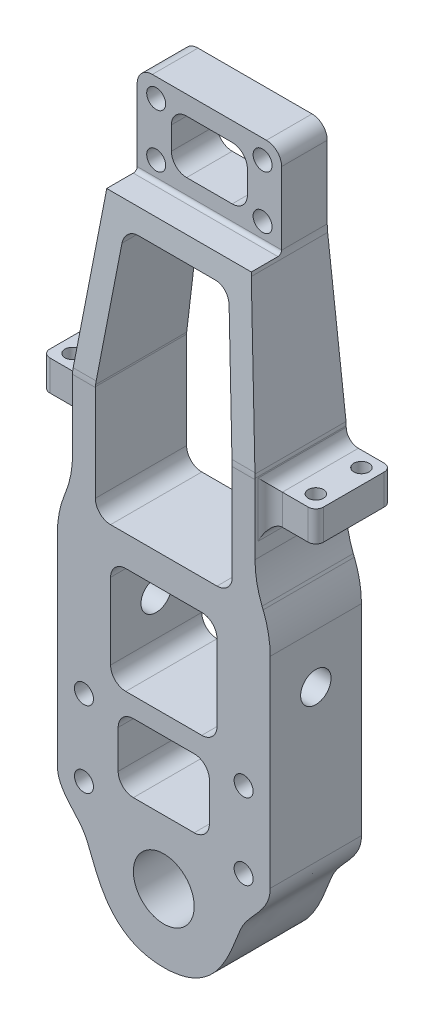
SolidWorks part; units mm, degrees
material "6061-T6 (SS)"
ref_plane "Front Plane" through (0, 0, 0) normal (0, 0, 1) x (1, 0, 0)
ref_plane "Top Plane" through (0, 0, 0) normal (0, 1, 0) x (1, 0, 0)
ref_plane "Right Plane" through (0, 0, 0) normal (1, 0, 0) x (0, 0, -1)
sketch "Sketch1" plane through (0, 0, 0) normal (0, 0, 1) x (1, 0, 0)
  line L0 (0, 0) -> (0, 168.402) construction
  line L1 (0, 0) -> (0, -85.725) construction
  line L2 (-22.225, 22.225) -> (22.225, 22.225)
  line L3 (-22.225, 22.225) -> (-22.225, -22.225)
  line L4 (-22.225, -22.225) -> (22.225, -22.225)
  line L5 (22.225, 22.225) -> (22.225, -22.225)
  line L6 (-38.1, 187.452) -> (38.1, 187.452) construction
  line L7 (-38.1, 187.452) -> (-38.1, -114.173) construction
  line L8 (-38.1, -114.173) -> (38.1, -114.173)
  line L9 (38.1, 187.452) -> (38.1, -114.173) construction
  line L10 (0, 0) -> (64.3201, 0) construction
  line L11 (-30.1625, 187.452) -> (-30.1625, 149.352)
  line L12 (-30.1625, 149.352) -> (-38.1, 82.55)
  line L13 (-38.1, 82.55) -> (-38.1, -114.173)
  line L15 (38.1, 82.55) -> (38.1, -114.173)
  line L16 (30.1625, 149.352) -> (38.1, 82.55)
  line L17 (30.1625, 187.452) -> (30.1625, 149.352)
  line L18 (-30.1625, 187.452) -> (30.1625, 187.452)
  circle A0 centre (0, -85.725) radius 12.7
  dimension "D10" = 25.4
  dimension "D1" = 168.402
  dimension "D2" = 28.448
  dimension "D3" = 44.45
  dimension "D4" = 44.45
  dimension "D5" = 301.625
  dimension "D6" = 76.2
  dimension "D7" = 38.1
  dimension "D8" = 19.05
  dimension "D9" = 85.725
  dimension "D11" = 60.325
  dimension "D12" = 82.55
  dimension "D13" = 66.802
extrude "Boss-Extrude1" add sketch "Sketch1" along normal blind 38.1
fillet "Fillet13" radius 25.4 2 edges at (30.1625, 149.352, 19.05) (-30.1625, 149.352, 19.05)
sketch "Sketch2" plane through (0, 0, 0) normal (1, 0, 0) x (0, 0, -1)
  line L0 (-19.05, 187.452) -> (-19.05, 149.352)
  line L2 (-19.05, 149.352) -> (-38.1, 149.352)
  line L4 (-38.1, 149.352) -> (-38.1, 187.452)
  line L5 (-38.1, 187.452) -> (-19.05, 187.452)
  line L6 (-38.1, 150.8557) -> (-38.1, 187.452) construction
  line L7 (-38.1, 187.452) -> (0, 187.452) construction
  dimension "D1" = 38.1
  dimension "D2" = 19.05
extrude "Cut-Extrude1" cut sketch "Sketch2" against normal through all and the other way through all
sketch "Sketch3" plane through (0, 0, 19.05) normal (0, 0, 1) x (1, 0, 0)
  line L1 (-30.1625, 168.402) -> (30.1625, 168.402) construction
  line L5 (0, 168.402) -> (0, 187.452) construction
  line L6 (-30.1625, 187.452) -> (30.1625, 187.452) construction
  line L7 (-30.1625, 150.8557) -> (-30.1625, 187.452) construction
  circle A0 centre (-22.225, 179.5145) radius 3.9688
  circle A1 centre (22.225, 179.5145) radius 3.9687
  circle A2 centre (-22.225, 157.2895) radius 3.9688
  circle A3 centre (22.225, 157.2895) radius 3.9687
  dimension "D9" = 7.9375
  dimension "D1" = 22.225
  dimension "D2" = 11.1125
extrude "Cut-Extrude2" cut sketch "Sketch3" against normal through all
sketch "Sketch4" plane through (-22.225, 0, 0) normal (1, 0, 0) x (0, 0, -1)
  line L1 (-38.1, 22.225) -> (-38.1, -22.225) construction
  circle A0 centre (-19.05, 0) radius 6.35
  dimension "D3" = 12.7
  dimension "D2" = 19.05
extrude "Cut-Extrude3" cut sketch "Sketch4" against normal through all and the other way through all
sketch "Sketch5" plane through (0, 0, 38.1) normal (0, 0, 1) x (1, 0, 0)
  line L0 (-38.1, -114.173) -> (-44.45, -114.173)
  line L1 (-44.45, -114.173) -> (-44.45, 28.575)
  line L2 (38.1, -114.173) -> (44.45, -114.173)
  line L3 (44.45, -114.173) -> (44.45, 28.575)
  line L4 (-44.45, 28.575) -> (-38.1, 44.45)
  line L5 (44.45, 28.575) -> (38.1, 44.45)
  line L6 (-38.1, 44.45) -> (-38.1, -114.173)
  line L7 (38.1, 44.45) -> (38.1, -114.173)
  line L8 (22.225, 22.225) -> (-22.225, 22.225) construction
  dimension "D1" = 6.35
  dimension "D3" = 22.225
  dimension "D4" = 15.875
extrude "Boss-Extrude2" add sketch "Sketch5" against normal up to surface (38.1 mm away) contours L1 L0 | L3 L2 region at (-41.2193, -38.7606, 38.1) region at (41.2193, -38.7606, 38.1) up to face at (26.1937, 157.2895, 0)
sketch "Sketch6" plane through (-22.225, 0, 0) normal (1, 0, 0) x (0, 0, -1)
  circle A0 centre (-19.05, 0) radius 6.35
  circle A1 centre (-19.05, 0) radius 6.35 construction
extrude "Cut-Extrude4" cut sketch "Sketch6" against normal through all and the other way through all
sketch "Sketch7" plane through (0, 0, 38.1) normal (0, 0, 1) x (1, 0, 0)
  line L0 (-28.575, 34.925) -> (-28.575, 81.9861) construction
  line L1 (-21.7023, 139.827) -> (21.7023, 139.827) construction
  line L2 (-28.575, 81.9861) -> (-21.7023, 139.827) construction
  line L3 (-28.575, 34.925) -> (28.575, 34.925) construction
  line L4 (28.575, 81.9861) -> (21.7023, 139.827) construction
  line L5 (28.575, 34.925) -> (28.575, 81.9861) construction
  line L6 (-30.2071, 149.352) -> (30.2071, 149.352) construction
  line L7 (22.225, 22.225) -> (-22.225, 22.225) construction
  line L8 (0, 0) -> (0, 134.3942) construction
  line L9 (-26.0738, 103.0362) -> (-35.5323, 104.1601) construction
  line L10 (-19.05, -30.48) -> (19.05, -30.48)
  line L11 (-19.05, -30.48) -> (-19.05, -59.055)
  line L12 (-19.05, -59.055) -> (19.05, -59.055)
  line L13 (19.05, -30.48) -> (19.05, -59.055)
  line L14 (-30.3399, 147.8588) -> (-38.1, 82.55) construction
  line L15 (-28.575, 61.5413) -> (-38.1, 61.5413) construction
  line L16 (-38.1, 82.55) -> (-38.1, 44.45) construction
  point P15 (0, 139.827)
  point P19 (0, 34.925)
  dimension "D1" = 9.525
  dimension "D2" = 38.1
  dimension "D3" = 9.525
  dimension "D4" = 12.7
  dimension "D5" = 30.48
  dimension "D6" = 28.575
  dimension "D7" = 57.15
extrude "Cut-Extrude5" cut sketch "Sketch7" against normal offset from surface (33.3375 mm away) 4.7625 up to face at (26.1937, 157.2895, 0)
sketch "Sketch20" plane through (0, 0, 38.1) normal (0, 0, 1) x (1, 0, 0)
  line L0 (-28.575, 81.9861) -> (-21.7023, 139.827) construction
  line L1 (-21.7023, 139.827) -> (21.7023, 139.827) construction
  line L2 (28.575, 81.9861) -> (21.7023, 139.827) construction
  line L3 (28.575, 34.925) -> (28.575, 81.9861) construction
  line L4 (-28.575, 34.925) -> (28.575, 34.925) construction
  line L5 (-28.575, 34.925) -> (-28.575, 81.9861) construction
  line L6 (-28.575, 81.9861) -> (-21.7023, 139.827)
  line L7 (-21.7023, 139.827) -> (21.7023, 139.827)
  line L8 (28.575, 81.9861) -> (21.7023, 139.827)
  line L9 (28.575, 34.925) -> (28.575, 81.9861)
  line L10 (-28.575, 34.925) -> (28.575, 34.925)
  line L11 (-28.575, 34.925) -> (-28.575, 81.9861)
extrude "Cut-Extrude13" cut sketch "Sketch20" against normal through all
fillet "Fillet1" radius 6.35 10 edges at (19.05, -59.055, 21.4313) (19.05, -30.48, 21.4313) (-19.05, -30.48, 21.4313) (-19.05, -59.055, 21.4313) (-28.575, 34.925, 19.05) (28.575, 34.925, 19.05) (21.7023, 139.827, 19.05) (-21.7023, 139.827, 19.05)
fillet "Fillet5" radius 41.275 4 edges at (44.45, 28.575, 19.05) (-44.45, 28.575, 19.05)
sketch "Sketch13" plane through (0, 0, 0) normal (1, 0, 0) x (0, 0, -1)
  circle A0 centre (-19.05, 0) radius 6.35 construction
  circle A1 centre (-19.05, 0) radius 6.35
sketch "Sketch14" plane through (0, 0, 38.1) normal (0, 0, 1) x (1, 0, 0)
  line L0 (0, 0) -> (0, -85.725) construction
  line L1 (56.1407, -47.625) -> (0, -47.625) construction
  line L2 (0, 0) -> (0, -85.725) construction
  circle A0 centre (33.3375, -31.75) radius 3.9687
  circle A1 centre (33.3375, -63.5) radius 3.9687
  circle A2 centre (-33.3375, -63.5) radius 3.9688
  circle A3 centre (-33.3375, -31.75) radius 3.9688
  dimension "D4" = 7.9375
  dimension "D1" = 47.625
  dimension "D2" = 31.75
  dimension "D3" = 66.675
extrude "Cut-Extrude9" cut sketch "Sketch14" against normal blind 19.05
fillet "Fillet4" radius 6.35 4 edges at (-22.225, -22.225, 19.05) (22.225, -22.225, 19.05) (22.225, 22.225, 19.05) (-22.225, 22.225, 19.05)
sketch "Sketch15" plane through (38.1, 0, 0) normal (1, 0, 0) x (0, 0, -1)
  line L1 (0, 52.3988) -> (0, 82.55) construction
  line L2 (0, 76.2) -> (-31.75, 76.2)
  line L3 (-31.75, 76.2) -> (-31.75, 63.5)
  line L4 (-31.75, 63.5) -> (0, 63.5)
  line L5 (-31.75, 69.85) -> (0, 69.85) construction
  line L6 (-15.875, 69.85) -> (-15.875, 6.3089) construction
  line L7 (0, 63.5) -> (0, 76.2)
  dimension "D1" = 12.7
  dimension "D2" = 31.75
  dimension "D3" = 69.85
extrude "Boss-Extrude3" add sketch "Sketch15" along normal blind 19.05
sketch "Sketch16" plane through (0, 76.2, 0) normal (0, 1, 0) x (1, 0, 0)
  line L0 (57.15, -15.875) -> (38.8119, -15.875) construction
  line L1 (57.15, 0) -> (57.15, -31.75) construction
  line L2 (50.8, -6.35) -> (50.8, -25.4) construction
  line L4 (45.2437, -9.5579) -> (50.8, -12.7658) construction
  line L5 (50.8, -12.7658) -> (56.3562, -9.5579) construction
  line L6 (56.3562, -9.5579) -> (56.3562, -3.1421) construction
  line L7 (56.3562, -3.1421) -> (50.8, 0.0658) construction
  line L8 (50.8, 0.0658) -> (45.2437, -3.1421) construction
  line L9 (45.2437, -3.1421) -> (45.2437, -9.5579) construction
  circle A0 centre (50.8, -6.35) radius 3.175
  circle A1 centre (50.8, -25.4) radius 3.175
  circle A2 centre (50.8, -6.35) radius 6.4158 construction
  point P8 (50.8, -15.875)
  dimension "D1" = 6.35
  dimension "D2" = 19.05
  dimension "D3" = 11.1125
  dimension "D4" = 6.35
extrude "Cut-Extrude10" cut sketch "Sketch16" against normal up to next
mirror "Mirror4" about plane through (0, 0, 0) normal (1, 0, 0) of "Cut-Extrude10", "Boss-Extrude3"
fillet "Fillet11" radius 12.7 2 edges at (-38.1, 82.55, 19.05) (38.1, 82.55, 19.05)
fillet "Fillet6" radius 5.08 4 edges at (-38.1, 76.2, 15.875) (-38.1, 63.5, 15.875) (38.1, 63.5, 15.875) (38.1, 76.2, 15.875)
fillet "Fillet7" radius 5.08 2 edges at (-38.1, 69.85, 31.75) (38.1, 69.85, 31.75)
fillet "Fillet8" radius 3.175 4 edges at (57.15, 69.85, 31.75) (-57.15, 69.85, 31.75) (57.15, 69.85, 0) (-57.15, 69.85, 0)
ref_point "Point1"
sketch "Sketch17" plane through (0, 0, 0) normal (0, 0, 1) x (1, 0, 0)
  line L0 (0, -85.725) -> (9.726, 37.8549)
  line L1 (0, -85.725) -> (0, 0) construction
  dimension "D1" = 4.5
chamfer "Chamfer1" distance 66.802 distance2 6.35 1 edges at (0, 149.352, 38.1) first distance on face at (-37.3062, -31.75, 38.1)
fillet "Fillet9" radius 25.4 2 edges at (-33.2929, 82.55, 38.1) (33.2929, 82.55, 38.1)
fillet "Fillet10" radius 1.5875 8 edges at (-17.1901, -32.3399, 4.7625) (-19.05, -44.7675, 4.7625) (-17.1901, -57.1951, 4.7625) (0, -59.055, 4.7625) (17.1901, -57.1951, 4.7625) (19.05, -44.7675, 4.7625) (17.1901, -32.3399, 4.7625) (0, -30.48, 4.7625)
sketch "Sketch18" plane through (0, 0, 38.1) normal (0, 0, 1) x (1, 0, 0)
  line L0 (-44.45, -114.173) -> (44.45, -114.173) construction
  line L1 (-44.45, -114.173) -> (-44.45, 20.6262) construction
  line L2 (44.45, -114.173) -> (44.45, 20.6262) construction
  line L3 (-44.45, -114.173) -> (44.45, -114.173)
  line L4 (-44.45, -114.173) -> (-44.45, -63.2897)
  line L5 (44.45, -114.173) -> (44.45, -63.2897)
  line L6 (0, -85.725) -> (0, 0) construction
  line L7 (-6.757, -114.173) -> (6.787, -114.173) construction
  line L8 (44.45, -70.2557) -> (44.45, -44.5652) construction
  line L9 (0, -114.173) -> (0, 0) construction
  circle A0 centre (0, -69.723) radius 44.45 construction
  circle A1 centre (0, -85.725) radius 25.4 construction
  spline S0 degree 3 poles (44.45, -63.2897) (44.45, -70.6109) (36.9805, -76.2293) (28.9235, -88.5672) (23.7898, -114.173) (0, -114.173) knots 0 0 0 0 0.400028 0.500028 1 1 1 1
  spline S1 degree 3 poles (-44.45, -63.2897) (-44.45, -70.6109) (-36.9805, -76.2293) (-28.9235, -88.5672) (-23.7898, -114.173) (0, -114.173) knots 0 0 0 0 0.400028 0.500028 1 1 1 1
  line M27 (-44.45, 20.6262) -> (-44.45, -114.173)
  line M28 (-44.45, -114.173) -> (44.45, -114.173)
  line M29 (44.45, -114.173) -> (44.45, 20.6262)
  dimension "D1" = 50.8
extrude "Cut-Extrude11" cut sketch "Sketch18" against normal through all contours S1 M27 M28 | S0 L3 M29 region at (-34.0613, -98.4284, 38.1) region at (34.0592, -98.4235, 38.1)
fillet "Fillet14" radius 6.35 2 edges at (-30.1625, 187.452, 9.525) (30.1625, 187.452, 9.525)
sketch "Sketch19" plane through (0, 0, 19.05) normal (0, 0, 1) x (1, 0, 0)
  line L0 (0, 0) -> (0, 202.3632) construction
  line L2 (-15.875, 179.5145) -> (15.875, 179.5145)
  line L3 (-15.875, 179.5145) -> (-15.875, 157.2895)
  line L4 (-15.875, 157.2895) -> (15.875, 157.2895)
  line L5 (15.875, 179.5145) -> (15.875, 157.2895)
  line L6 (-15.875, 179.5145) -> (15.875, 157.2895) construction
  line L7 (-15.875, 157.2895) -> (15.875, 179.5145) construction
  point P3 (0, 168.402)
  dimension "D1" = 31.75
  dimension "D2" = 22.225
extrude "Cut-Extrude12" cut sketch "Sketch19" against normal through all
fillet "Fillet15" radius 6.35 4 edges at (-15.875, 157.2895, 9.525) (-15.875, 179.5145, 9.525) (15.875, 179.5145, 9.525) (15.875, 157.2895, 9.525)
sketch "Sketch21" plane through (0, 0, 38.1) normal (0, 0, 1) x (1, 0, 0)
  line L42 (-15.875, 15.875) -> (-15.875, -15.875)
  line L43 (-15.875, 15.875) -> (-15.875, -15.875) construction
  line L48 (15.875, 15.875) -> (-15.875, 15.875)
  line L49 (15.875, 15.875) -> (-15.875, 15.875) construction
  line L51 (15.875, -15.875) -> (15.875, 15.875)
  line L52 (15.875, -15.875) -> (15.875, 15.875) construction
  line L54 (-15.875, -15.875) -> (15.875, -15.875)
  line L55 (-15.875, -15.875) -> (15.875, -15.875) construction
  line L57 (12.7, -36.83) -> (-12.7, -36.83)
  line L58 (12.7, -36.83) -> (-12.7, -36.83) construction
  line L60 (-12.7, -36.83) -> (-12.7, -52.705)
  line L61 (-12.7, -36.83) -> (-12.7, -52.705) construction
  line L67 (-12.7, -52.705) -> (12.7, -52.705)
  line L68 (12.7, -52.705) -> (12.7, -36.83)
  line L69 (-12.7, -52.705) -> (12.7, -52.705) construction
  line L70 (12.7, -52.705) -> (12.7, -36.83) construction
  dimension "D1" = 6.35
  dimension "D2" = 6.35
  dimension "D3" = 6.35
  dimension "D4" = 6.35
  dimension "D5" = 6.35
  dimension "D6" = 6.35
  dimension "D7" = 6.35
fillet "Fillet16" radius 1.5875 1 edges at (0, 149.352, 19.05)
